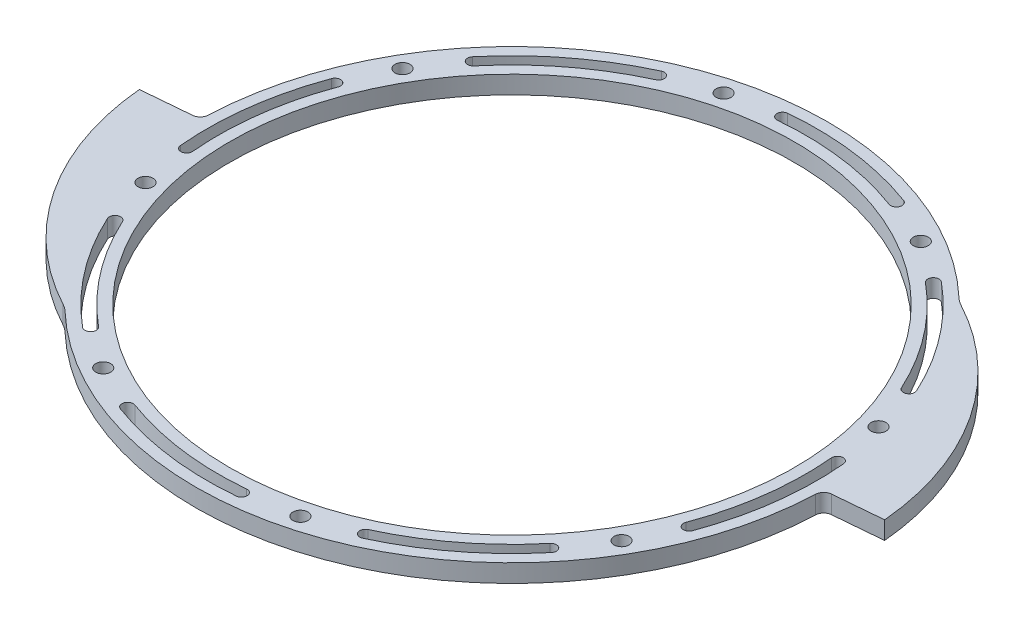
SolidWorks part; units mm, degrees
material "Alloy Steel"
ref_plane "Front Plane" through (0, 0, 0) normal (0, 0, 1) x (1, 0, 0)
ref_plane "Top Plane" through (0, 0, 0) normal (0, 1, 0) x (1, 0, 0)
ref_plane "Right Plane" through (0, 0, 0) normal (1, 0, 0) x (0, 0, -1)
sketch "Sketch1" plane through (0, 0, 0) normal (0, 1, 0) x (1, 0, 0)
  line L0 (0, 0) -> (-132, 0) construction
  line L1 (-132.0082, 0.0941) -> (-134.7743, 31.7103) construction
  line L2 (-111.9863, 1.751) -> (-132, 0)
  line L3 (-132, 0) -> (-132, 32.0934) construction
  line L4 (-129.3938, 0) -> (-182.8754, 0) construction
  line L5 (-112, 0) -> (-132, 0) construction
  line L6 (-79.4774, -79.4774) -> (0, 0) construction
  circle A0 centre (0, 0) radius 100
  arc A10 (-132, 0) -> (-79.4774, -79.4774) centre (-32.4231, 8.7118) ccw
  arc A11 (-79.4774, -79.4774) -> (-77.2845, -81.0624) centre (-84.1849, -88.3001) cw
  arc A12 (-77.2845, -81.0624) -> (-111.9863, 1.751) centre (0, 0) ccw
  dimension "D1" = 200
  dimension "D6" = 10
  dimension "D4" = 5
  dimension "D7" = 45
  dimension "D2" = 12
  dimension "D3" = 5
  dimension "D5" = 20
extrude "Boss-Extrude1" add sketch "Sketch1" along normal mid plane 6.35
fillet "Fillet1" radius 3 1 edges at (-111.9863, 0, -1.751)
pattern_circular "CirPattern1" count 2 over 360 about axis through (0, 3.175, 0) along (0, -1, 0) of "Boss-Extrude1", "Fillet1" reverse direction yes
sketch "Sketch2" plane through (0, 3.175, 0) normal (0, 1, 0) x (1, 0, 0)
  line L0 (-102.3881, -27.4348) -> (0, 0) construction
  line L1 (0, 0) -> (-106, 0) construction
  circle A0 centre (-102.3881, -27.4348) radius 2.65
  circle A2 centre (0, 0) radius 106 construction
  circle A3 centre (0, 0) radius 100 construction
  dimension "D3" = 5.3
  dimension "D1" = 106
  dimension "D2" = 6
  dimension "D4" = 15
extrude "Cut-Extrude1" cut sketch "Sketch2" against normal through all
pattern_circular "CirPattern2" count 8 over 360 about axis through (0, 3.175, 0) along (0, -1, 0) of "Cut-Extrude1"
sketch "Sketch3" plane through (0, 3.175, 0) normal (0, 1, 0) x (1, 0, 0)
  line L0 (-102.3881, -27.4348) -> (0, 0) construction
  line L1 (-102.3881, -27.4348) -> (0, 0) construction
  line L2 (0, 0) -> (-91.7987, 53) construction
  line L3 (-105.0932, 13.8358) -> (0, 0) construction
  arc A0 (-105.5538, -9.7154) -> (-99.4426, 36.7037) centre (0, 0) cw construction
  circle A1 centre (0, 0) radius 106 construction
  arc A2 (-101.3189, 37.3962) -> (-107.5454, -9.8987) centre (0, 0) ccw
  arc A3 (-97.5664, 36.0112) -> (-103.5622, -9.5321) centre (0, 0) ccw
  arc A4 (-97.5664, 36.0112) -> (-101.3189, 37.3962) centre (-99.4426, 36.7037) ccw
  arc A5 (-107.5454, -9.8987) -> (-103.5622, -9.5321) centre (-105.5538, -9.7154) ccw
  point P3 (-105.0932, 13.8358)
  dimension "D4" = 2
  dimension "D1" = 45
  dimension "D2" = 22.5
  dimension "D3" = 18
extrude "Lightening Cut" cut sketch "Sketch3" against normal through all
pattern_circular "Lightening Pattern" count 8 over 360 about axis through (0, 3.175, 0) along (0, -1, 0) of "Lightening Cut"
equation "\"ring_id\"=200"
equation "\"D1@Sketch1\"=\"ring_id\""
equation "\"D2@Sketch2\"=\"D2@Sketch1\"/2"
equation "\"D2@Sketch3\"=\"D1@Sketch3\"/2"
